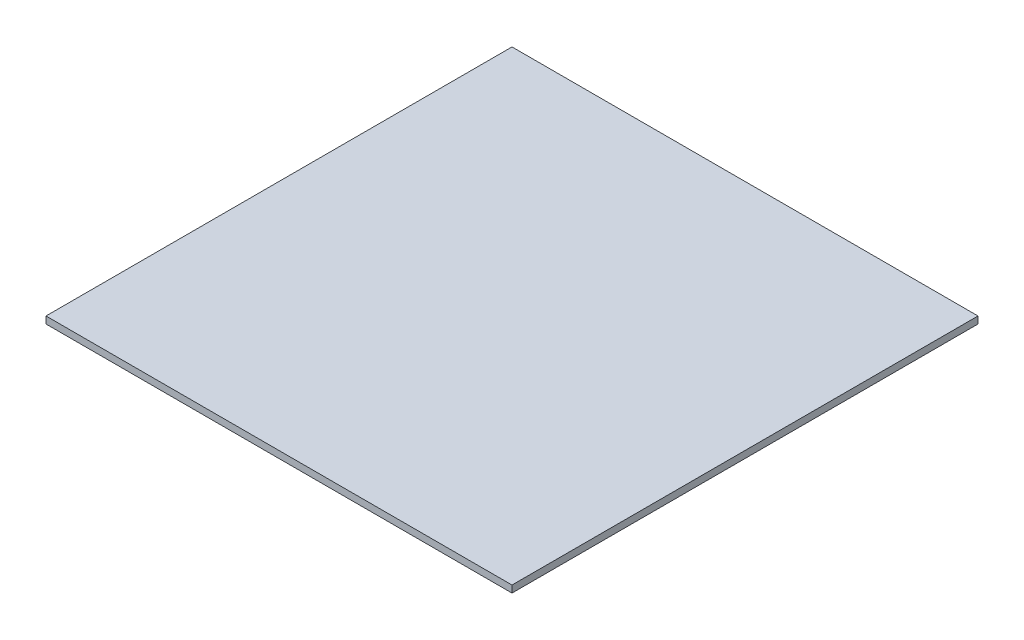
SolidWorks part; units mm, degrees
material "Copper"
ref_plane "Спереди" through (0, 0, 0) normal (0, 0, 1) x (1, 0, 0)
ref_plane "Сверху" through (0, 0, 0) normal (0, 1, 0) x (1, 0, 0)
ref_plane "Справа" through (0, 0, 0) normal (1, 0, 0) x (0, 0, -1)
sketch "Sketch1" plane through (0, 0, 0) normal (0, 1, 0) x (1, 0, 0)
  line L1 (0, 0) -> (200, 0)
  line L2 (0, 0) -> (0, 200)
  line L3 (0, 200) -> (200, 200)
  line L4 (200, 0) -> (200, 200)
  dimension "D1" = 200
  dimension "D2" = 200
extrude "Boss-Extrude1" add sketch "Sketch1" along normal blind 3
